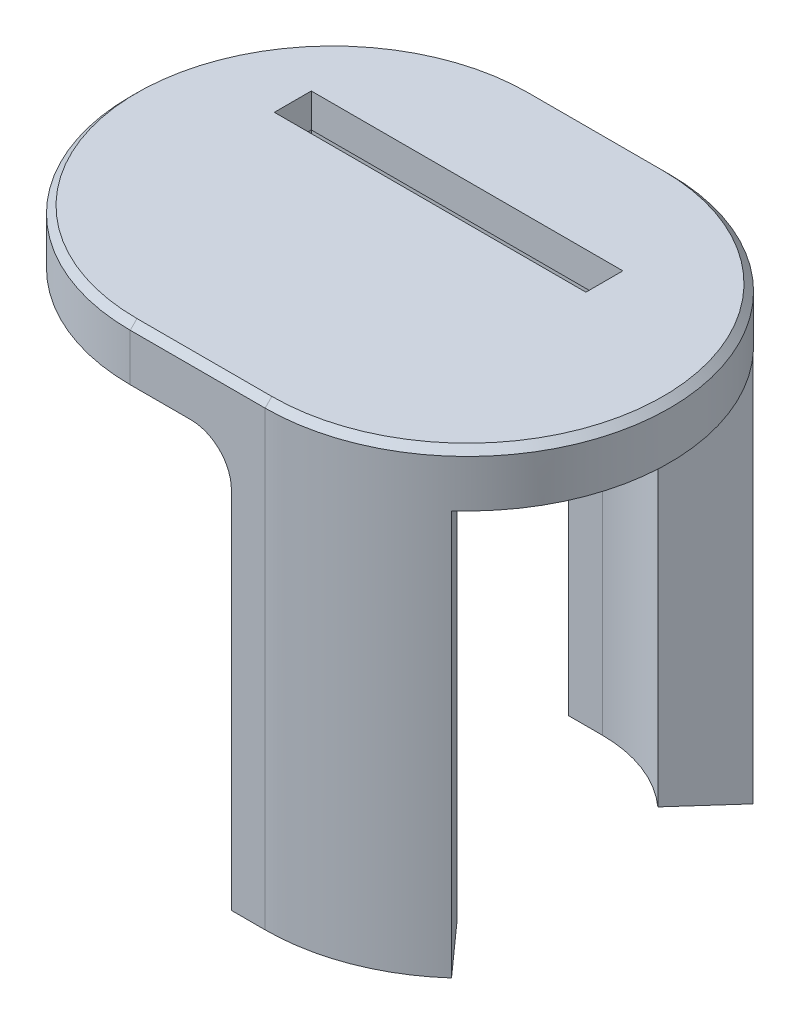
SolidWorks part; units mm, degrees
ref_plane "Ebene vorne" through (0, 0, 0) normal (0, 0, 1) x (1, 0, 0)
ref_plane "Ebene oben" through (0, 0, 0) normal (0, 1, 0) x (1, 0, 0)
ref_plane "Ebene rechts" through (0, 0, 0) normal (1, 0, 0) x (0, 0, -1)
sketch "Skizze1" plane through (0, 0, 0) normal (0, 1, 0) x (1, 0, 0)
  line L0 (5, 15) -> (5, 0) construction
  line L1 (5, 0) -> (5, -15) construction
  line L2 (5, 15) -> (2.5, 15)
  line L3 (2.5, 15) -> (2.5, 10)
  line L4 (2.5, 10) -> (5, 10)
  line L5 (5, 0) -> (15, 11.1803) construction
  line L6 (5, 0) -> (20, 0) construction
  line L7 (5, 0) -> (15, -11.1803) construction
  line L8 (15, 11.1803) -> (15, -11.1803) construction
  line L9 (11.6667, 7.4536) -> (15, 11.1803)
  line L10 (11.6667, -7.4536) -> (15, -11.1803)
  line L11 (5, -10) -> (2.5, -10)
  line L12 (2.5, -10) -> (2.5, -15)
  line L13 (2.5, -15) -> (5, -15)
  arc A3 (5, -15) -> (5, 15) centre (5, 0) ccw construction
  arc A4 (5, 15) -> (15, 11.1803) centre (5, 0) cw
  arc A5 (5, 10) -> (11.6667, 7.4536) centre (5, 0) cw
  arc A6 (5, -15) -> (15, -11.1803) centre (5, 0) ccw
  arc A7 (5, -10) -> (11.6667, -7.4536) centre (5, 0) ccw
  dimension "D2" = 15
  dimension "D3" = 10
  dimension "D1" = 5
  dimension "D4" = 5
  dimension "D5" = 2.5
extrude "Aufsatz-Linear austragen1" add sketch "Skizze1" against normal blind 30
sketch "Skizze2" plane through (0, 0, 0) normal (0, 1, 0) x (1, 0, 0)
  line L0 (5, 15) -> (5, -15) construction
  line L1 (-5, 0) -> (5, 0) construction
  line L2 (-5, 15) -> (5, 15)
  line L3 (-5, -15) -> (5, -15)
  arc A0 (-5, 15) -> (-5, -15) centre (-5, 0) ccw
  arc A1 (5, -15) -> (5, 15) centre (5, 0) ccw
  point P6 (0, 0)
  dimension "D1" = 5
extrude "Aufsatz-Linear austragen2" add sketch "Skizze2" along normal blind 4
fillet "Verrundung1" radius 3 4 edges at (3.75, 0, 10) (8.5682, 0, 9.3417) (8.5682, 0, -9.3417) (3.75, 0, -10)
fillet "Verrundung2" radius 3 2 edges at (2.5, 0, 11) (2.5, 0, -11)
chamfer "Fase1" distance 0.5 angle 45 4 edges at (-20, 4, 0) (0, 4, 15) (0, 4, -15) (20, 4, 0)
sketch "Skizze3" plane through (0, -30, 0) normal (0, -1, 0) x (1, 0, 0)
  line L0 (0, 0) -> (20, 0) construction
  line L1 (11.6667, -7.4536) -> (15, -11.1803) construction
  line L3 (9.6442, -11.6052) -> (5, 0) construction
  line L4 (5, 0) -> (13.3333, -9.3169) construction
  line L5 (9.6667, -5.2175) -> (15, -11.1803) construction
  line L6 (9.6442, 11.6052) -> (5, 0) construction
  line L7 (5, 0) -> (13.3333, 9.3169) construction
  arc A0 (15, -11.1803) -> (15, 11.1803) centre (5, 0) ccw construction
  circle A1 centre (9.6442, -11.6052) radius 1.25
  circle A2 centre (9.6442, -11.6052) radius 2.5 construction
  arc A3 (5, -10) -> (11.6667, -7.4536) centre (5, 0) ccw construction
  arc A4 (5, -15) -> (15, -11.1803) centre (5, 0) ccw construction
  arc A5 (9.6442, -11.6052) -> (13.3333, -9.3169) centre (5, 0) ccw construction
  arc A7 (9.6442, 11.6052) -> (13.3333, 9.3169) centre (5, 0) cw construction
  circle A8 centre (9.6442, 11.6052) radius 2.5 construction
  circle A9 centre (9.6442, 11.6052) radius 1.25
  dimension "D1" = 2.5
  dimension "D2" = 20
extrude "Schnitt-Linear austragen1" cut sketch "Skizze3" against normal blind 8
sketch "Skizze4" plane through (0, 4, 0) normal (0, 1, 0) x (1, 0, 0)
  line L0 (9.9475, 6.5752) -> (-13.1525, 6.5752)
  line L1 (9.8475, 6.4752) -> (-13.0525, 6.4752) construction
  line L2 (9.8475, 6.4752) -> (9.8475, 3.9352) construction
  line L3 (9.8475, 3.9352) -> (-13.0525, 3.9352) construction
  line L4 (-13.0525, 6.4752) -> (-13.0525, 3.9352) construction
  line L5 (-13.1525, 6.5752) -> (-13.1525, 3.8352)
  line L6 (9.9475, 3.8352) -> (-13.1525, 3.8352)
  line L7 (9.9475, 6.5752) -> (9.9475, 3.8352)
  dimension "D1" = 0.1
extrude "Schnitt-Linear austragen2" cut sketch "Skizze4" along direction (0, 1, 0) on the side against the normal blind 2.5
sketch "Skizze5" plane through (0, 1.5, 0) normal (0, 1, 0) x (1, 0, 0)
  line L8 (10.1475, 3.6352) -> (10.1475, 6.7752)
  line L9 (10.1475, 6.7752) -> (-13.3525, 6.7752)
  line L10 (-13.3525, 6.7752) -> (-13.3525, 3.6352)
  line L11 (-13.3525, 3.6352) -> (10.1475, 3.6352)
  line L12 (10.1475, 3.6352) -> (10.1475, 6.7752)
  line L13 (10.1475, 6.7752) -> (-13.3525, 6.7752)
  line L14 (-13.3525, 6.7752) -> (-13.3525, 3.6352)
  line L15 (-13.3525, 3.6352) -> (10.1475, 3.6352)
  dimension "D1" = 0.2
extrude "Schnitt-Linear austragen3" cut sketch "Skizze5" against normal up to next
